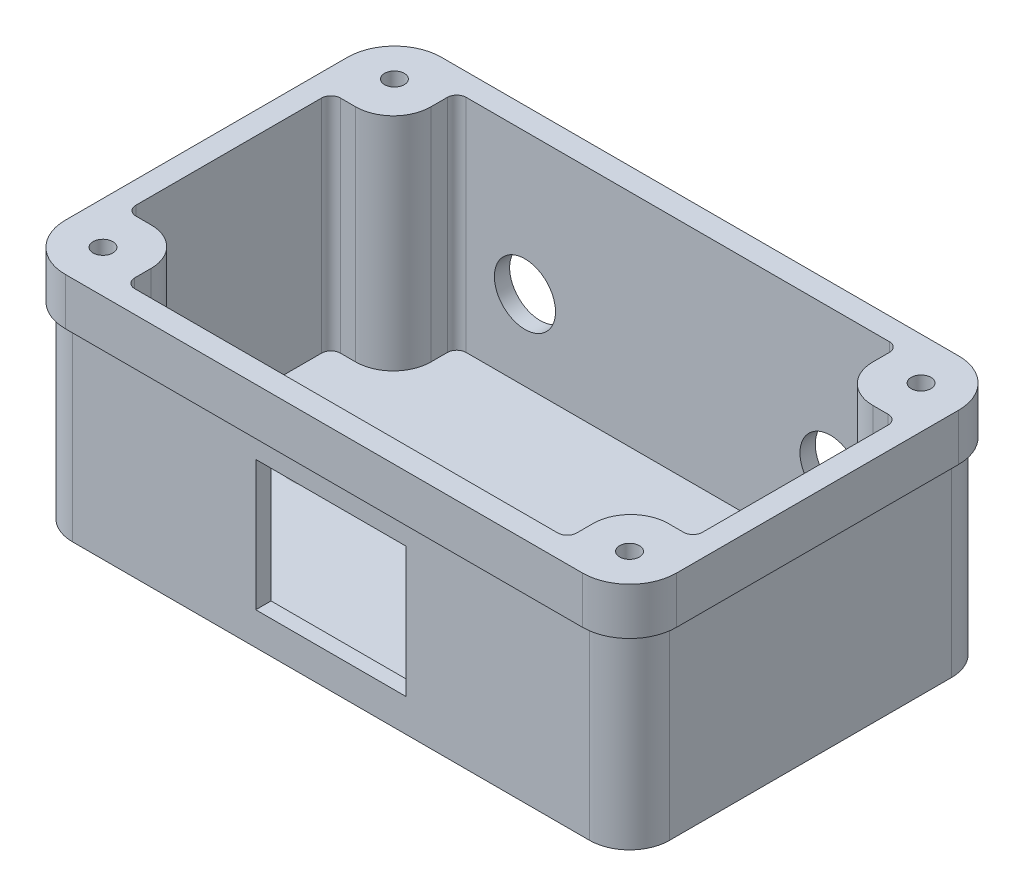
SolidWorks part; units mm, degrees
ref_plane "Front Plane" through (0, 0, 0) normal (0, 0, 1) x (1, 0, 0)
ref_plane "Top Plane" through (0, 0, 0) normal (0, 1, 0) x (1, 0, 0)
ref_plane "Right Plane" through (0, 0, 0) normal (1, 0, 0) x (0, 0, -1)
sketch "Sketch1" plane through (0, 0, 0) normal (0, 1, 0) x (1, 0, 0)
  line L1 (-55, 40) -> (55, 40)
  line L2 (-65, 30) -> (-65, -30)
  line L3 (-55, -40) -> (55, -40)
  line L4 (65, 30) -> (65, -30)
  line L5 (-65, 40) -> (65, -40) construction
  line L6 (-65, -40) -> (65, 40) construction
  arc A0 (-65, -30) -> (-55, -40) centre (-55, -30) ccw
  arc A1 (55, -40) -> (65, -30) centre (55, -30) ccw
  arc A2 (55, 40) -> (65, 30) centre (55, 30) cw
  arc A3 (-55, 40) -> (-65, 30) centre (-55, 30) ccw
  point P0 (0, 0)
  dimension "D3" = 10
  dimension "D1" = 130
  dimension "D2" = 80
extrude "Boss-Extrude1" add sketch "Sketch1" along normal blind 50
shell "Shell1" thickness 3 removed face at (0, 50, 0)
sketch "Sketch2" plane through (0, 0, 0) normal (0, -1, 0) x (1, 0, 0)
  line L0 (-63.5, 30) -> (-63.5, -30)
  line L1 (-55, -38.5) -> (55, -38.5)
  line L2 (63.5, -30) -> (63.5, 30)
  line L3 (55, 38.5) -> (-55, 38.5)
  line L8 (65, -30) -> (65, 30)
  line L9 (55, 40) -> (-55, 40)
  line L10 (-65, 30) -> (-65, -30)
  line L11 (-55, -40) -> (55, -40)
  line L12 (65, -30) -> (65, 30)
  line L13 (55, 40) -> (-55, 40)
  line L14 (-65, 30) -> (-65, -30)
  line L15 (-55, -40) -> (55, -40)
  arc A0 (-55, 38.5) -> (-63.5, 30) centre (-55, 30) ccw
  arc A1 (-63.5, -30) -> (-55, -38.5) centre (-55, -30) ccw
  arc A2 (55, -38.5) -> (63.5, -30) centre (55, -30) ccw
  arc A3 (63.5, 30) -> (55, 38.5) centre (55, 30) ccw
  arc A4 (-55, 40) -> (-65, 30) centre (-55, 30) ccw
  arc A5 (-55, 40) -> (-65, 30) centre (-55, 30) ccw
  arc A6 (-65, -30) -> (-55, -40) centre (-55, -30) ccw
  arc A7 (-65, -30) -> (-55, -40) centre (-55, -30) ccw
  arc A8 (55, -40) -> (65, -30) centre (55, -30) ccw
  arc A9 (55, -40) -> (65, -30) centre (55, -30) ccw
  arc A10 (65, 30) -> (55, 40) centre (55, 30) ccw
  arc A11 (65, 30) -> (55, 40) centre (55, 30) ccw
  dimension "D1" = 0
  dimension "D2" = 1.5
extrude "Cut-Extrude1" cut sketch "Sketch2" against normal blind 40
sketch "Sketch3" plane through (0, 3, 0) normal (0, 1, 0) x (1, 0, 0)
  line L4 (0, 40) -> (0, -40) construction
  line L9 (55, 40) -> (-55, 40) construction
  line L16 (-55, -40) -> (55, -40) construction
  line L17 (-65, 0) -> (65, 0) construction
  line L18 (-65, 30) -> (-65, -30) construction
  line L19 (65, -30) -> (65, 30) construction
  line L20 (-58.25, 21.75) -> (-55, 21.75)
  line L21 (-45, 35.25) -> (45, 35.25)
  line L22 (-60.25, 19.75) -> (-60.25, -19.75)
  line L23 (-45, -35.25) -> (45, -35.25)
  line L24 (60.25, 19.75) -> (60.25, -19.75)
  line L25 (-60.25, 35.25) -> (60.25, -35.25) construction
  line L26 (-60.25, -35.25) -> (60.25, 35.25) construction
  line L27 (-47, 29.75) -> (-47, 33.25)
  line L28 (47, 29.75) -> (47, 33.25)
  line L29 (58.25, 21.75) -> (55, 21.75)
  line L30 (47, -29.75) -> (47, -33.25)
  line L31 (58.25, -21.75) -> (55, -21.75)
  line L32 (-58.25, -21.75) -> (-55, -21.75)
  line L33 (-47, -29.75) -> (-47, -33.25)
  line L34 (62, -30) -> (62, 30) construction
  line L35 (-55, -37) -> (55, -37) construction
  line L36 (-62, 30) -> (-62, -30) construction
  line L37 (55, 37) -> (-55, 37) construction
  line L38 (62, -30) -> (62, 30)
  line L39 (-55, -37) -> (55, -37)
  line L40 (-62, 30) -> (-62, -30)
  line L41 (55, 37) -> (-55, 37)
  circle A8 centre (-56, 31) radius 2.1
  circle A9 centre (56, 31) radius 2.1
  circle A10 centre (56, -31) radius 2.1
  circle A11 centre (-56, -31) radius 2.1
  arc A12 (-55, -21.75) -> (-47, -29.75) centre (-55, -29.75) cw
  arc A13 (47, -29.75) -> (55, -21.75) centre (55, -29.75) cw
  arc A14 (47, 29.75) -> (55, 21.75) centre (55, 29.75) ccw
  arc A15 (-55, 21.75) -> (-47, 29.75) centre (-55, 29.75) ccw
  arc A16 (-47, -33.25) -> (-45, -35.25) centre (-45, -33.25) ccw
  arc A17 (-60.25, -19.75) -> (-58.25, -21.75) centre (-58.25, -19.75) ccw
  arc A18 (45, -35.25) -> (47, -33.25) centre (45, -33.25) ccw
  arc A19 (58.25, -21.75) -> (60.25, -19.75) centre (58.25, -19.75) ccw
  arc A20 (60.25, 19.75) -> (58.25, 21.75) centre (58.25, 19.75) ccw
  arc A21 (45, 35.25) -> (47, 33.25) centre (45, 33.25) cw
  arc A22 (-60.25, 19.75) -> (-58.25, 21.75) centre (-58.25, 19.75) cw
  arc A23 (-45, 35.25) -> (-47, 33.25) centre (-45, 33.25) ccw
  arc A24 (62, 30) -> (55, 37) centre (55, 30) ccw construction
  arc A25 (55, -37) -> (62, -30) centre (55, -30) ccw construction
  arc A26 (-62, -30) -> (-55, -37) centre (-55, -30) ccw construction
  arc A27 (-55, 37) -> (-62, 30) centre (-55, 30) ccw construction
  arc A28 (62, 30) -> (55, 37) centre (55, 30) ccw
  arc A29 (55, -37) -> (62, -30) centre (55, -30) ccw
  arc A30 (-62, -30) -> (-55, -37) centre (-55, -30) ccw
  arc A31 (-55, 37) -> (-62, 30) centre (-55, 30) ccw
  point P22 (0, 0)
  point P41 (-47, -21.75)
  point P44 (47, -21.75)
  point P47 (47, 21.75)
  point P50 (-47, 21.75)
  dimension "D1" = 4.2
  dimension "D8" = 8
  dimension "D5" = 2
  dimension "D2" = 112
  dimension "D3" = 62
  dimension "D4" = 120.5
  dimension "D6" = 43.5
  dimension "D7" = 94
extrude "Boss-Extrude5" add sketch "Sketch3" along normal blind 47 separate body
sketch "Sketch5" plane through (0, 3, 0) normal (0, 1, 0) x (1, 0, 0)
  line L0 (-65, 0) -> (65, 0) construction
  line L1 (-65, 30) -> (-65, -30) construction
  line L2 (65, -30) -> (65, 30) construction
  line L3 (0, 40) -> (0, -40) construction
  line L4 (55, 40) -> (-55, 40) construction
  line L5 (-55, -40) -> (55, -40) construction
  circle A0 centre (-40, 0) radius 2
  circle A1 centre (40, 0) radius 2
  dimension "D1" = 4
  dimension "D2" = 80
extrude "Cut-Extrude2" cut sketch "Sketch5" against normal blind 10
sketch "Sketch6" plane through (0, 3, 0) normal (0, 1, 0) x (1, 0, 0)
  line L4 (0, 40) -> (0, -40) construction
  line L5 (55, 40) -> (-55, 40) construction
  line L6 (-55, -40) -> (55, -40) construction
  circle A4 centre (-40, 0) radius 2 construction
  circle A8 centre (-40, 0) radius 2
  circle A9 centre (-40, 0) radius 6
  circle A10 centre (40, 0) radius 2
  circle A11 centre (40, 0) radius 6
  dimension "D1" = 12
extrude "Boss-Extrude6" add sketch "Sketch6" along normal blind 3
fillet "Fillet1" radius 1 4 edges at (40, 6, -6) (40, 3, -6) (-40, 6, 6) (-40, 3, 6)
sketch "Sketch7" plane through (0, 0, 38.5) normal (0, 0, 1) x (1, 0, 0)
  line L0 (0, 0) -> (0, 50) construction
  line L1 (55, 0) -> (-55, 0) construction
  line L2 (-55, 50) -> (55, 50) construction
  line L4 (-16, 34.6803) -> (16, 34.6803)
  line L5 (-16, 34.6803) -> (-16, 6.9803)
  line L6 (-16, 6.9803) -> (16, 6.9803)
  line L7 (16, 34.6803) -> (16, 6.9803)
  line L8 (-16, 34.6803) -> (16, 6.9803) construction
  line L9 (-16, 6.9803) -> (16, 34.6803) construction
  point P6 (0, 20.8303)
  dimension "D1" = 32
  dimension "D2" = 27.7
extrude "Cut-Extrude3" cut sketch "Sketch7" against normal blind 10
sketch "Sketch8" plane through (0, 0, -38.5) normal (0, 0, -1) x (-1, 0, 0)
  line L0 (0, 40) -> (0, 0) construction
  line L1 (55, 40) -> (-55, 40) construction
  circle A0 centre (-32.5, 20) radius 6.5
  circle A1 centre (32.5, 20) radius 6.5
  dimension "D2" = 13
  dimension "D1" = 65
extrude "Cut-Extrude4" cut sketch "Sketch8" against normal blind 10
